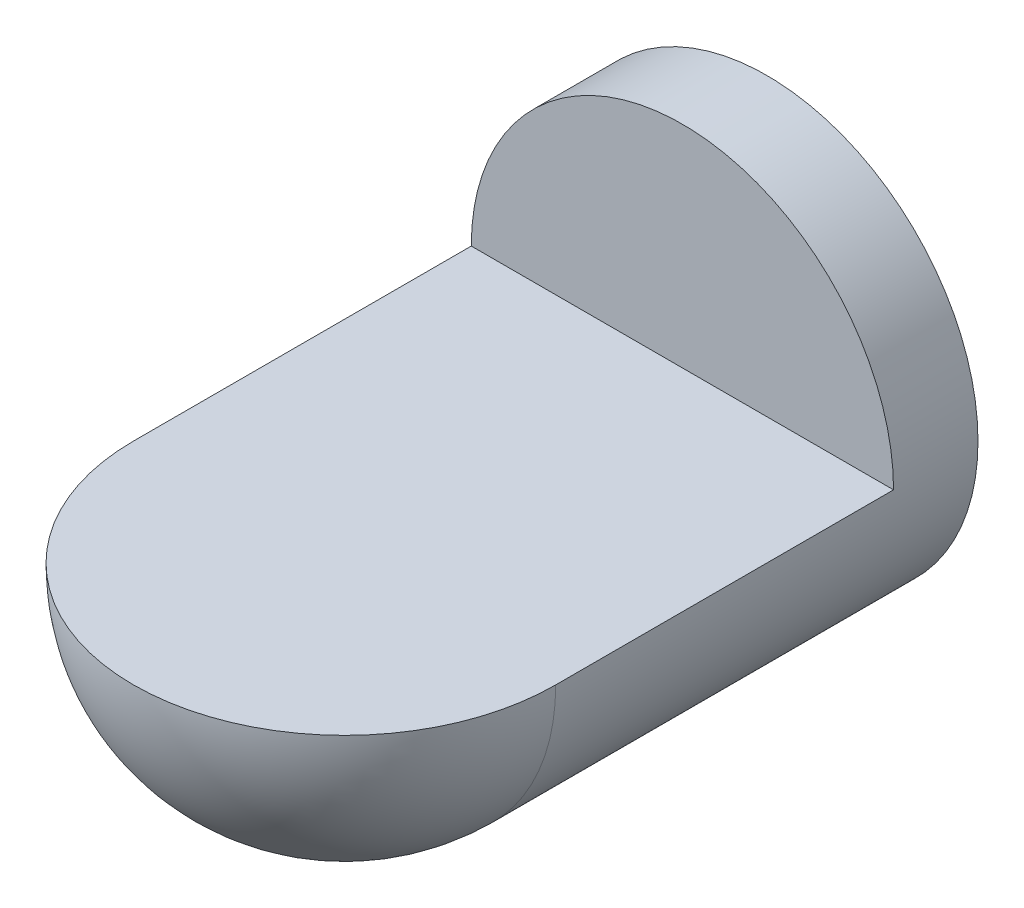
SolidWorks part; units mm, degrees
ref_plane "Front Plane" through (0, 0, 0) normal (0, 0, 1) x (1, 0, 0)
ref_plane "Top Plane" through (0, 0, 0) normal (0, 1, 0) x (1, 0, 0)
ref_plane "Right Plane" through (0, 0, 0) normal (1, 0, 0) x (0, 0, -1)
sketch "Sketch1" plane through (0, 0, 0) normal (1, 0, 0) x (0, 0, -1)
  line L0 (-146.9091, 0) -> (313.5945, 0) construction
  line L1 (150, 0) -> (-75, 0)
  line L2 (150, 0) -> (150, 75)
  line L3 (0, 75) -> (150, 75)
  arc A0 (-75, 0) -> (0, 75) centre (0, 0) cw
  dimension "D1" = 75
  dimension "D2" = 150
revolve "Revolve1" add sketch "Sketch1" angle 360 about L0
sketch "Sketch2" plane through (0, 0, 0) normal (1, 0, 0) x (0, 0, -1)
  line L0 (-88.0407, 0) -> (120.4455, 0) construction
  line L1 (120, 0) -> (120, 75)
  line L2 (150, 75) -> (0, 75) construction
  line L3 (120, 0) -> (-75, 0)
  line L4 (120, 75) -> (0, 75)
  line L5 (150, -75) -> (150, 75) construction
  arc A0 (0, 75) -> (0, -75) centre (0, 0) ccw construction
  arc A1 (-75, 0) -> (0, 75) centre (0, 0) cw
  dimension "D1" = 30
extrude "Cut-Extrude1" cut sketch "Sketch2" along normal through all and the other way through all
ref_axis "Axis1" through (0, 82.5, 0) along (0, -1, 0)
equation "\"base_link_length\"=150"
equation "\"link1_diameter\"=150"
equation "\"D1@Sketch1\"=\"link1_diameter\"/2"
equation "\"link1_length\"=150"
equation "\"D2@Sketch1\"=\"link1_length\""
equation "\"link2_diameter\"=150"
equation "\"link2_length\"=300"
equation "\"link3_diameter\"=150"
equation "\"link3_length\"=150"
equation "\"link4_diameter\"=150"
equation "\"link4_length\"=150"
equation "\"link5_diameter\"=150"
equation "\"link5_length\"=200"
equation "\"end_effector_diameter\"=150"
equation "\"end_effector_length\"=150"
equation "\"base_link_diameterA\"=200"
equation "\"base_link_diameterB\"=150"
equation "\"base_link_lengthA\"=50"
